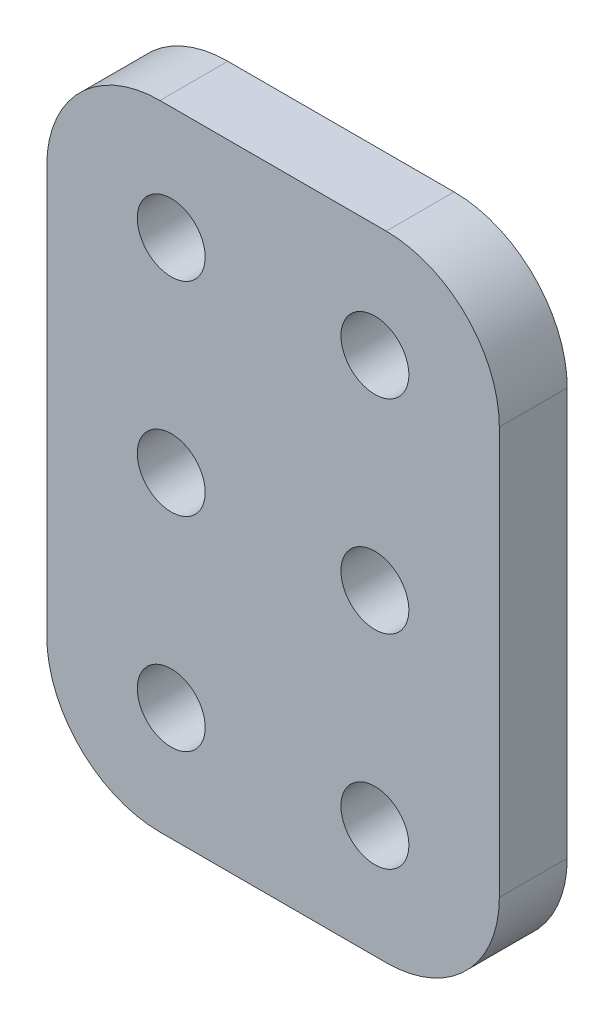
SolidWorks part; units mm, degrees
material "6061-T6 (SS)"
ref_plane "Front Plane" through (0, 0, 0) normal (0, 0, 1) x (1, 0, 0)
ref_plane "Top Plane" through (0, 0, 0) normal (0, 1, 0) x (1, 0, 0)
ref_plane "Right Plane" through (0, 0, 0) normal (1, 0, 0) x (0, 0, -1)
ref_axis "X" through (-88.99, 0, 0) along (1, 0, 0)
ref_axis "Y" through (0, 55, 0) along (0, -1, 0)
ref_axis "Z" through (0, 0, -88.99) along (0, 0, 1)
sketch "Sketch1" plane through (0, 0, 0) normal (0, 0, 1) x (1, 0, 0)
  line L1 (-10, 14) -> (10, 14)
  line L2 (-10, 14) -> (-10, -14)
  line L3 (-10, -14) -> (10, -14)
  line L4 (10, 14) -> (10, -14)
  line L5 (-10, 14) -> (10, -14) construction
  line L6 (-10, -14) -> (10, 14) construction
  point P0 (0, 0)
  dimension "D1" = 28
  dimension "D2" = 20
extrude "Boss-Extrude1" add sketch "Sketch1" along normal blind 3
sketch "Sketch2" plane through (0, 0, 0) normal (0, 0, -1) x (-1, 0, 0)
  circle A0 centre (4.5, -9) radius 1.5 construction
  circle A1 centre (-4.5, -9) radius 1.5 construction
  circle A2 centre (-4.5, 0) radius 1.5 construction
  circle A3 centre (4.5, 0) radius 1.5 construction
  circle A4 centre (4.5, 9) radius 1.5 construction
  circle A5 centre (-4.5, 9) radius 1.5 construction
  circle A6 centre (4.5, -9) radius 1.5
  circle A7 centre (-4.5, -9) radius 1.5
  circle A8 centre (-4.5, 0) radius 1.5
  circle A9 centre (4.5, 0) radius 1.5
  circle A10 centre (4.5, 9) radius 1.5
  circle A11 centre (-4.5, 9) radius 1.5
extrude "Cut-Extrude1" cut sketch "Sketch2" against normal through all
fillet "Fillet1" radius 5 4 edges at (-10, -14, 1.5) (10, -14, 1.5) (-10, 14, 1.5) (10, 14, 1.5)
